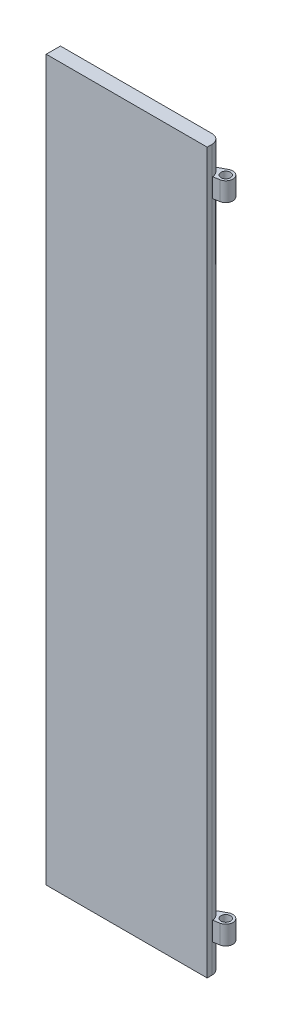
SolidWorks part; units mm, degrees
ref_plane "Płaszczyzna przednia" through (0, 0, 0) normal (0, 0, 1) x (1, 0, 0)
ref_plane "Płaszczyzna górna" through (0, 0, 0) normal (0, 1, 0) x (1, 0, 0)
ref_plane "Płaszczyzna prawa" through (0, 0, 0) normal (1, 0, 0) x (0, 0, -1)
sketch "Szkic1" plane through (0, 0, 0) normal (0, 0, 1) x (1, 0, 0)
  line L1 (0, 0) -> (340, 0)
  line L2 (0, 0) -> (0, 1520)
  line L3 (0, 1520) -> (340, 1520)
  line L4 (340, 0) -> (340, 1520)
  dimension "D1" = 1520
  dimension "D2" = 340
extrude "Dodanie-wyciągnięcie1" add sketch "Szkic1" along normal blind 30
fillet "Zaokrąglenie1" radius 20 1 edges at (340, 760, 0)
sketch "Szkic3" plane through (0, 1520, 0) normal (0, 1, 0) x (1, 0, 0)
  line L9 (343.569, 11.8523) -> (317.5798, -2.0149)
  line L10 (317.5798, -2.0149) -> (327.4713, -20.5532)
  line L11 (327.4713, -20.5532) -> (353.1551, -16.1677)
  circle A1 centre (350.6303, -1.3817) radius 10
  arc A6 (353.1551, -16.1677) -> (343.569, 11.8523) centre (350.6303, -1.3817) ccw
extrude "Dodanie-wyciągnięcie2" add sketch "Szkic3" against normal blind 40 from offset 60 offset against normal yes
ref_plane "Płaszczyzna1" through (0, 760, 0) normal (0, -1, 0) x (-1, 0, 0)
mirror "Lustro1" about plane through (0, 760, 0) normal (0, -1, 0) of "Dodanie-wyciągnięcie2"
